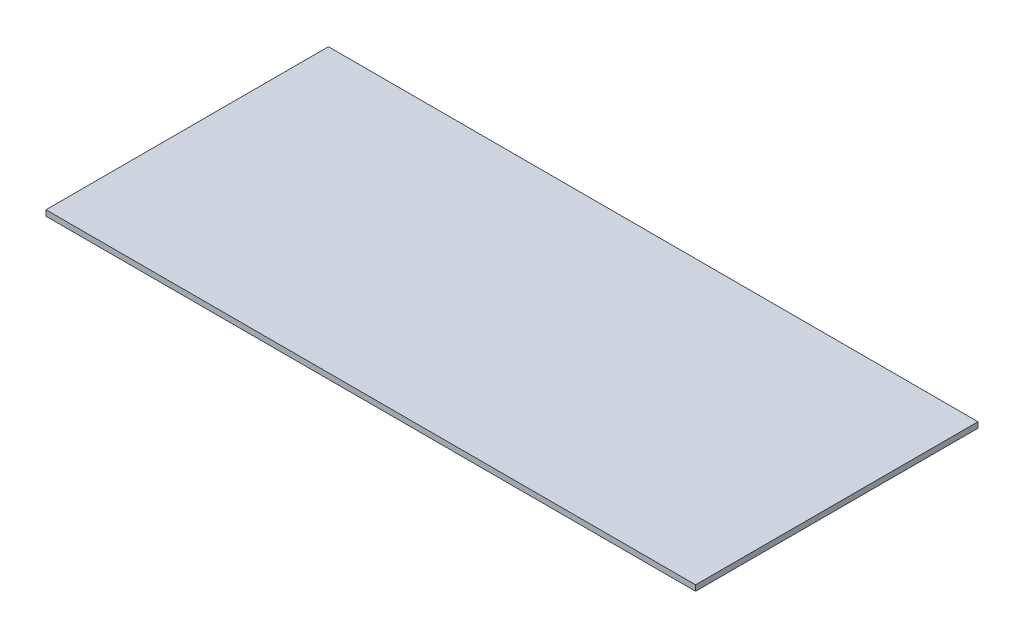
SolidWorks part; units mm, degrees
material "ABS"
ref_plane "Front Plane" through (0, 0, 0) normal (0, 0, 1) x (1, 0, 0)
ref_plane "Top Plane" through (0, 0, 0) normal (0, 1, 0) x (1, 0, 0)
ref_plane "Right Plane" through (0, 0, 0) normal (1, 0, 0) x (0, 0, -1)
sketch "Sketch1" plane through (0, 0, 0) normal (0, 1, 0) x (1, 0, 0)
  line L1 (0, 0) -> (2300, 0)
  line L2 (0, 0) -> (0, 1000)
  line L3 (0, 1000) -> (2300, 1000)
  line L4 (2300, 0) -> (2300, 1000)
  dimension "D1" = 1000
  dimension "D2" = 2300
extrude "Boss-Extrude1" add sketch "Sketch1" along normal blind 20
